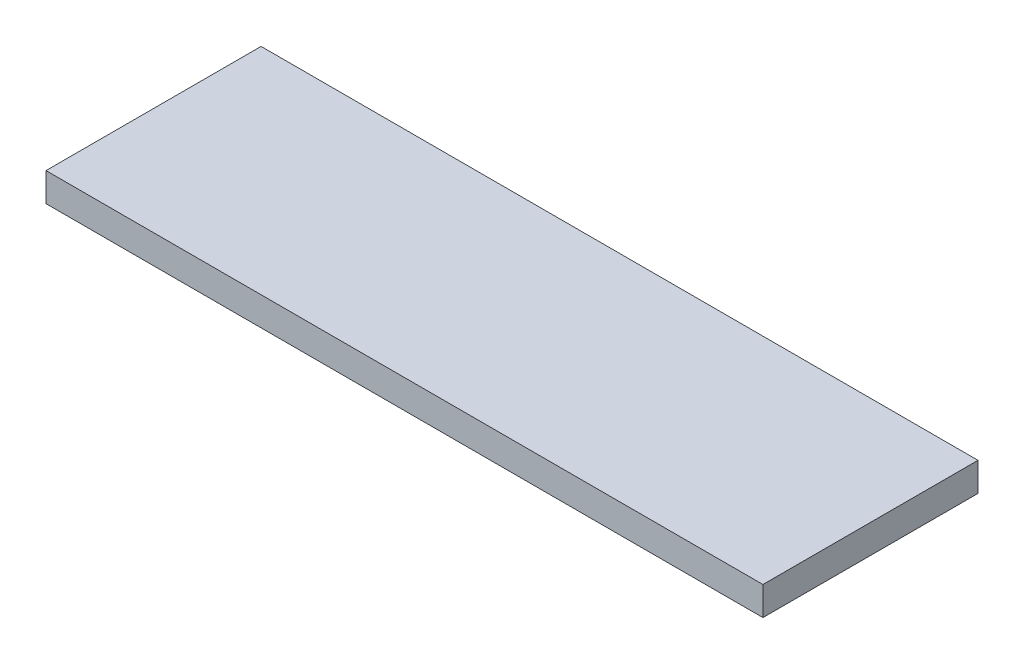
SolidWorks part; units mm, degrees
ref_plane "Plan de face" through (0, 0, 0) normal (0, 0, 1) x (1, 0, 0)
ref_plane "Plan de dessus" through (0, 0, 0) normal (0, 1, 0) x (1, 0, 0)
ref_plane "Plan de droite" through (0, 0, 0) normal (1, 0, 0) x (0, 0, -1)
sketch "Esquisse1" plane through (0, 0, 0) normal (0, 1, 0) x (1, 0, 0)
  line L1 (-250, 75) -> (250, 75)
  line L2 (-250, 75) -> (-250, -75)
  line L3 (-250, -75) -> (250, -75)
  line L4 (250, 75) -> (250, -75)
  line L5 (-250, 75) -> (250, -75) construction
  line L6 (-250, -75) -> (250, 75) construction
  point P0 (0, 0)
  dimension "D1" = 500
  dimension "D2" = 150
extrude "Boss.-Extru.1" add sketch "Esquisse1" along normal blind 20
sketch "Esquisse2" plane through (0, 20, 0) normal (0, 1, 0) x (1, 0, 0)
  line L0 (-250, 75) -> (-250, -75) construction
  line L1 (-250, 55) -> (250, 55)
  line L2 (-250, 55) -> (-250, 35)
  line L3 (-250, 35) -> (250, 35)
  line L4 (250, 55) -> (250, 35)
  line L5 (250, -75) -> (250, 75) construction
  line L6 (250, 75) -> (-250, 75) construction
  dimension "D1" = 20
  dimension "D2" = 20
